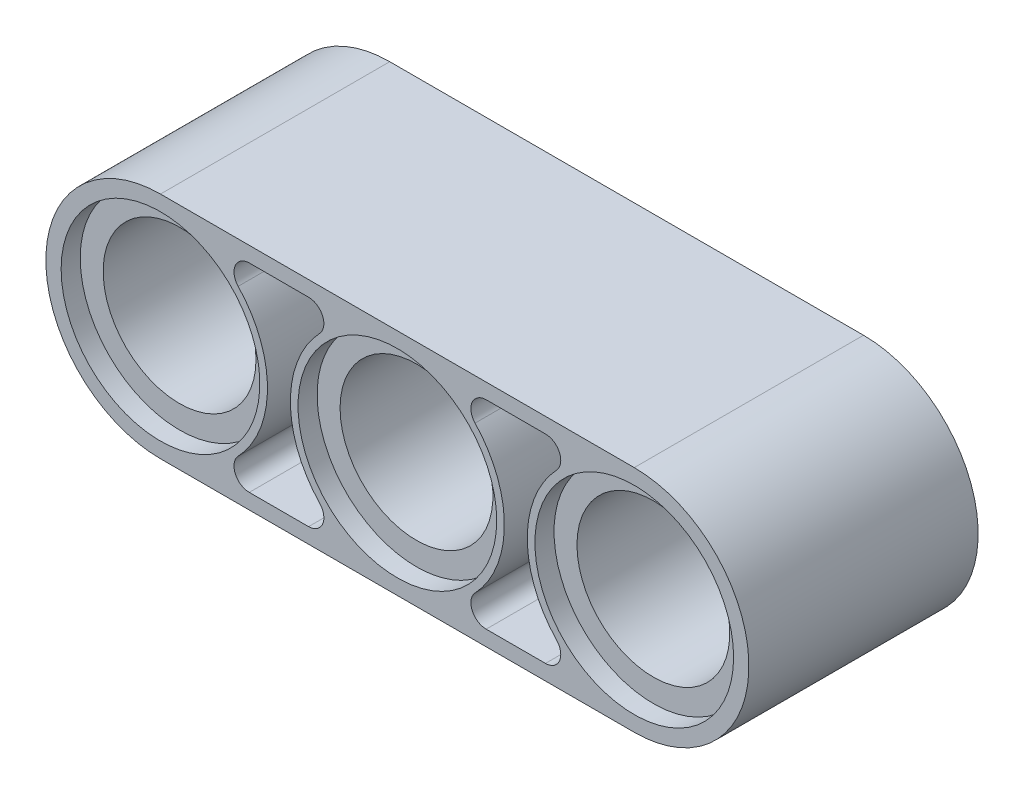
SolidWorks part; units mm, degrees
material "PVC Rigid"
ref_plane "Front Plane" through (0, 0, 0) normal (0, 0, 1) x (1, 0, 0)
ref_plane "Top Plane" through (0, 0, 0) normal (0, 1, 0) x (1, 0, 0)
ref_plane "Right Plane" through (0, 0, 0) normal (1, 0, 0) x (0, 0, -1)
sketch "Sketch1" plane through (0, 0, 0) normal (0, 0, 1) x (1, 0, 0)
  line L0 (-7.874, 0) -> (7.874, 0) construction
  line L1 (7.874, -3.81) -> (-7.874, -3.81)
  line L2 (7.874, 3.81) -> (-7.874, 3.81)
  line L8 (0, 15.1379) -> (0, -14.3507)
  line L9 (3.937, 3.302) -> (3.937, -3.302) construction
  line L10 (3.937, 3.302) -> (3.937, 3.81)
  line L11 (2.9512, -3.302) -> (4.9228, -3.302)
  line L12 (2.9512, 3.302) -> (4.9228, 3.302)
  line L13 (3.937, -3.302) -> (3.937, -3.81)
  line L14 (-3.937, 3.302) -> (-3.937, -3.302) construction
  line L15 (-3.937, -3.302) -> (-3.937, -3.81)
  line L16 (-2.9512, 3.302) -> (-4.9228, 3.302)
  line L17 (-2.9512, -3.302) -> (-4.9228, -3.302)
  line L18 (-3.937, 3.302) -> (-3.937, 3.81)
  arc A0 (7.874, -3.81) -> (7.874, 3.81) centre (7.874, 0) ccw
  circle A1 centre (0, 0) radius 3.302
  circle A2 centre (0, 0) radius 2.54
  circle A3 centre (7.874, 0) radius 3.302
  circle A4 centre (7.874, 0) radius 2.54
  arc A5 (-2.9512, 3.302) -> (-2.5823, 2.4447) centre (-2.9512, 2.794) cw
  arc A7 (-4.9228, 3.302) -> (-5.2917, 2.4447) centre (-4.9228, 2.794) ccw
  arc A8 (-5.2917, -2.4447) -> (-4.9228, -3.302) centre (-4.9228, -2.794) ccw
  arc A11 (2.5823, -2.4448) -> (2.5823, 2.4447) centre (0, 0) ccw
  arc A12 (5.2917, 2.4447) -> (5.2917, -2.4447) centre (7.874, 0) ccw
  arc A13 (2.5823, -2.4448) -> (2.9512, -3.302) centre (2.9512, -2.794) ccw
  arc A14 (-2.5823, -2.4448) -> (-2.9512, -3.302) centre (-2.9512, -2.794) cw
  arc A15 (-5.2917, 2.4447) -> (-5.2917, -2.4447) centre (-7.874, 0) cw
  arc A16 (5.2917, -2.4447) -> (4.9228, -3.302) centre (4.9228, -2.794) cw
  arc A17 (4.9228, 3.302) -> (5.2917, 2.4447) centre (4.9228, 2.794) cw
  arc A18 (2.9512, 3.302) -> (2.5823, 2.4447) centre (2.9512, 2.794) ccw
  arc A19 (-2.5823, -2.4448) -> (-2.5823, 2.4447) centre (0, 0) cw
  circle A20 centre (-7.874, 0) radius 2.54
  circle A21 centre (-7.874, 0) radius 3.302
  arc A22 (-7.874, -3.81) -> (-7.874, 3.81) centre (-7.874, 0) cw
  point P13 (9.525, 0)
  point P14 (0, -3.81)
  point P15 (7.62, 0)
  point P17 (0, 3.302)
  point P18 (19.05, 3.302)
  point P19 (0, -3.302)
  point P20 (19.05, -3.302)
  point P23 (13.843, 0)
  point P25 (23.368, 0)
  point P26 (3.429, 0)
  point P27 (-7.874, -3.302)
  point P28 (7.874, -3.302)
  point P29 (-7.874, 3.302)
  point P30 (7.874, 3.302)
  point P35 (11.811, 0)
  point P60 (11.5175, 1.1139)
  point P67 (0, 3.81)
  dimension "D2" = 7.62
  dimension "D3" = 0.508
  dimension "D4" = 5.08
  dimension "D6" = 11.684
  dimension "D1" = 0.254
  dimension "D5" = 0.508
extrude "Boss-Extrude1" add sketch "Sketch1" along normal blind 3.81 contours A3 A4 | L12 A17 A12 A16 L11 A0 A3 region at (5.9055, -3.7013, 0) region at (4.6654, 0, 0)
ref_plane "Plane2" through (11.684, 0, 0) normal (1, 0, 0) x (0, 0, -1)
extrude "Boss-Extrude2" add sketch "Sketch1<7>" along normal blind 3.81 separate body contours L8 A1 | A2 L8 A1 | A18 L12 L8 A1 L11 A13 A11 | A2 L8 A1 region at (1.9685, -3.7242, 0) region at (-1.9685, -3.7242, 0) region at (-3.2282, 0, 0) region at (0.0738, -2.921, 0)
sketch "Sketch1<7>" plane through (0, 0, 0) normal (0, 0, 1) x (1, 0, 0) same geometry as "Sketch1"
sketch "Sketch2" plane through (0, 0, 0) normal (0, 0, 1) x (1, 0, 0)
  circle A0 centre (7.874, 0) radius 3.302 construction
  circle A1 centre (0, 0) radius 3.302 construction
  circle A2 centre (7.874, 0) radius 3.302
  circle A3 centre (0, 0) radius 3.302
extrude "Cut-Extrude1" cut sketch "Sketch2" along normal blind 0.635
pattern_linear "LPattern1" [suppressed] count 1 spacing 7.874 of bodies 110
ref_plane "Plane1" through (0, 0, 0) normal (1, 0, 0) x (0, 0, -1)
mirror "Mirror2" about plane through (0, 0, 0) normal (1, 0, 0) of bodies 109 101
combine bodies "Combine1" operation type add bodies to combine 109 106 110
ref_plane "Plane3" through (0, 0, 3.81) normal (0, 0, 1) x (1, 0, 0)
mirror "Mirror3" about plane through (0, 0, 3.81) normal (0, 0, 1) of bodies 108
ref_plane "Plane4" through (-11.684, 0, 0) normal (-1, 0, 0) x (0, 0, 1)
